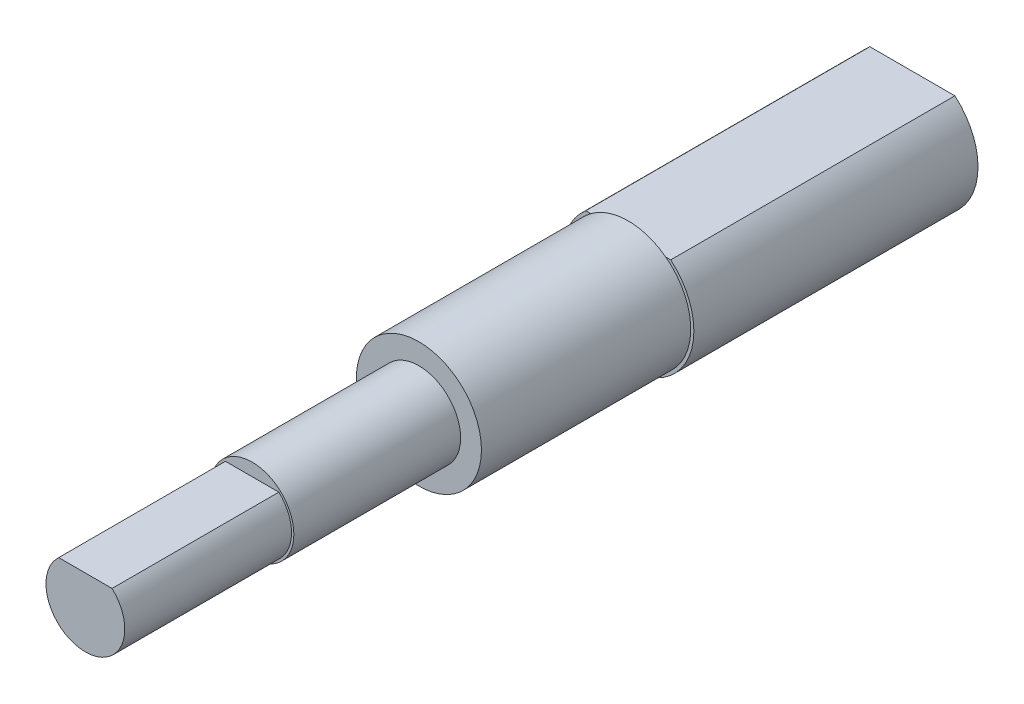
SolidWorks part; units mm, degrees
material "1060 Alloy"
ref_plane "Front" through (0, 0, 0) normal (0, 0, 1) x (1, 0, 0)
ref_plane "Top" through (0, 0, 0) normal (0, 1, 0) x (1, 0, 0)
ref_plane "Right" through (0, 0, 0) normal (1, 0, 0) x (0, 0, -1)
sketch "Sketch1" plane through (0, 0, 0) normal (0, 0, 1) x (1, 0, 0)
  circle A0 centre (0, 0) radius 5
  dimension "D1" = 10
extrude "Boss-Extrude1" add sketch "Sketch1" along normal blind 21.6375
sketch "Sketch2" plane through (0, 0, 21.6375) normal (0, 0, 1) x (1, 0, 0)
  circle A0 centre (0, 0) radius 4.7625
  dimension "D1" = 9.525
extrude "Boss-Extrude2" add sketch "Sketch2" along normal blind 15.9385
sketch "Sketch3" plane through (0, 0, 37.576) normal (0, 0, 1) x (1, 0, 0)
  circle A0 centre (0, 0) radius 3.175
  dimension "D1" = 6.35
extrude "Boss-Extrude3" add sketch "Sketch3" along normal blind 12.7
sketch "Sketch4" plane through (0, 0, 0) normal (0, 0, -1) x (-1, 0, 0)
  line L0 (0, 0) -> (0, 5) construction
  line L2 (12.7, 3.8094) -> (-12.7, 3.8094)
  line L3 (12.7, 3.8094) -> (12.7, 6.1906)
  line L4 (12.7, 6.1906) -> (-12.7, 6.1906)
  line L5 (-12.7, 3.8094) -> (-12.7, 6.1906)
  line L6 (12.7, 3.8094) -> (-12.7, 6.1906) construction
  line L7 (12.7, 6.1906) -> (-12.7, 3.8094) construction
  circle A0 centre (0, 0) radius 5 construction
  dimension "D1" = 2.3813
  dimension "D2" = 25.4
extrude "Cut-Extrude1" cut sketch "Sketch4" against normal up to surface (21.6375 mm away) up to face at (4.7625, 0, 21.6375)
sketch "Sketch5" plane through (0, 0, 50.276) normal (0, 0, 1) x (1, 0, 0)
  line L0 (0, 0) -> (0, 3.175) construction
  line L2 (12.7, 2.3813) -> (-12.7, 2.3812)
  line L3 (12.7, 2.3813) -> (12.7, 3.9688)
  line L4 (12.7, 3.9688) -> (-12.7, 3.9687)
  line L5 (-12.7, 2.3812) -> (-12.7, 3.9687)
  line L6 (12.7, 2.3813) -> (-12.7, 3.9687) construction
  line L7 (12.7, 3.9688) -> (-12.7, 2.3812) construction
  circle A0 centre (0, 0) radius 3.175 construction
  dimension "D1" = 1.5875
  dimension "D2" = 25.4
sketch "Sketch6" plane through (0, 0, 50.276) normal (0, 0, 1) x (1, 0, 0)
  circle A0 centre (0, 0) radius 3
  dimension "D1" = 6
extrude "Boss-Extrude4" add sketch "Sketch6" along normal blind 12.7
sketch "Sketch7" plane through (0, 0, 62.976) normal (0, 0, 1) x (1, 0, 0)
  line L0 (0, 0) -> (0, 3) construction
  line L2 (12.6863, 2.2063) -> (-12.6863, 2.2062)
  line L3 (12.6863, 2.2063) -> (12.6863, 3.7938)
  line L4 (12.6863, 3.7938) -> (-12.6863, 3.7937)
  line L5 (-12.6863, 2.2062) -> (-12.6863, 3.7937)
  line L6 (12.6863, 2.2063) -> (-12.6863, 3.7937) construction
  line L7 (12.6863, 3.7938) -> (-12.6863, 2.2062) construction
  circle A0 centre (0, 0) radius 3 construction
  dimension "D1" = 1.5875
  dimension "D2" = 25.3725
extrude "Cut-Extrude3" cut sketch "Sketch7" against normal up to surface (12.7 mm away) up to face at (3, 0, 50.276)
